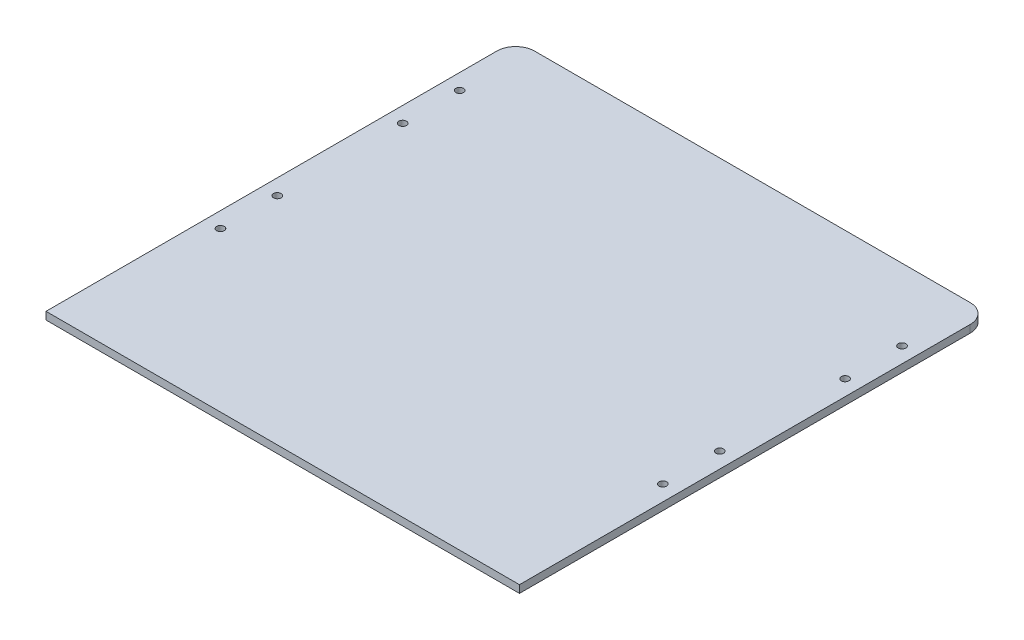
SolidWorks part; units mm, degrees
material "Medium density fiberboard, parallel to board"
ref_plane "Alzado" through (0, 0, 0) normal (0, 0, 1) x (1, 0, 0)
ref_plane "Planta" through (0, 0, 0) normal (0, 1, 0) x (1, 0, 0)
ref_plane "Vista lateral" through (0, 0, 0) normal (1, 0, 0) x (0, 0, -1)
sketch "Croquis1" plane through (0, 0, 0) normal (0, 1, 0) x (1, 0, 0)
  line L1 (-125, -124) -> (125, -124)
  line L2 (-125, -124) -> (-125, 114)
  line L3 (-115, 124) -> (115, 124)
  line L4 (125, -124) -> (125, 114)
  line L5 (-125, -124) -> (125, 124) construction
  line L6 (-125, 124) -> (125, -124) construction
  arc A0 (115, 124) -> (125, 114) centre (115, 114) cw
  arc A1 (-125, 114) -> (-115, 124) centre (-115, 114) cw
  point P0 (0, 0)
  dimension "D3" = 10
  dimension "D1" = 250
  dimension "D2" = 248
extrude "Saliente-Extruir1" add sketch "Croquis1" along normal mid plane 4
sketch "Croquis2" plane through (0, 2, 0) normal (0, 1, 0) x (1, 0, 0)
  line L0 (115, 124) -> (-115, 124) construction
  line L1 (-125, 114) -> (-125, -124) construction
  line L2 (-125, -124) -> (125, -124) construction
  line L3 (0, 48.6661) -> (0, -35.7913) construction
  circle A0 centre (-116.8, 86.2) radius 2
  circle A1 centre (-116.8, 56.15) radius 2
  circle A2 centre (-116.8, -10.05) radius 2
  circle A3 centre (-116.8, -40.1) radius 2
  circle A4 centre (116.8, -40.1) radius 2
  circle A5 centre (116.8, -10.05) radius 2
  circle A6 centre (116.8, 56.15) radius 2
  circle A7 centre (116.8, 86.2) radius 2
  dimension "D5" = 4
  dimension "D6" = 4
  dimension "D7" = 4
  dimension "D8" = 4
  dimension "D1" = 37.8
  dimension "D2" = 30.05
  dimension "D3" = 66.2
  dimension "D4" = 30.05
  dimension "D9" = 8.2
  dimension "D10" = 83.9
  dimension "D11" = 116.8
  dimension "D12" = 8.2
extrude "Cortar-Extruir1" cut sketch "Croquis2" against normal blind 10
